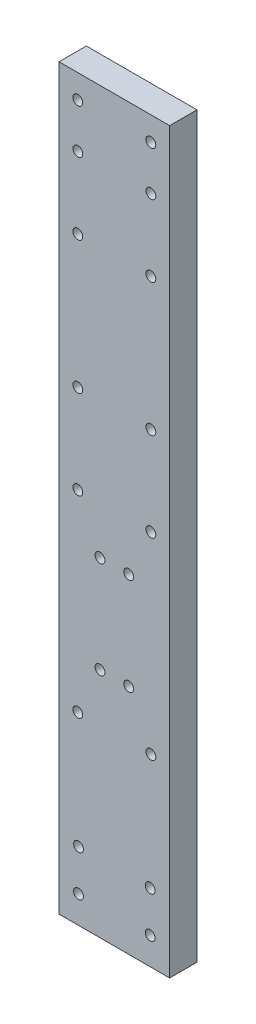
SolidWorks part; units mm, degrees
ref_plane "Front Plane" through (0, 0, 0) normal (0, 0, 1) x (1, 0, 0)
ref_plane "Top Plane" through (0, 0, 0) normal (0, 1, 0) x (1, 0, 0)
ref_plane "Right Plane" through (0, 0, 0) normal (1, 0, 0) x (0, 0, -1)
sketch "Sketch1" plane through (0, 0, 0) normal (0, 0, 1) x (1, 0, 0)
  line L0 (16.2, 0) -> (16.2, 108.14)
  line L1 (16.2, 108.14) -> (0, 108.14)
  line L2 (0, 108.14) -> (0, 0)
  line L3 (0, 0) -> (16.2, 0)
  line L4 (16.2, 57.71) -> (0, 57.71) construction
  line L5 (0, 12.5) -> (16.2, 12.5) construction
  line L6 (0, 24.5) -> (16.2, 24.5) construction
  line L7 (0, 90.16) -> (16.2, 90.16) construction
  line L8 (0, 65.71) -> (16.2, 65.71) construction
  line L9 (8.1, 108.14) -> (8.1, 96.16) construction
  line L11 (0, 96.16) -> (16.2, 96.16) construction
  circle A0 centre (13.45, 55.21) radius 0.72
  circle A1 centre (10.2, 48.21) radius 0.72
  circle A2 centre (13.45, 104.66) radius 0.72
  circle A3 centre (2.75, 98.16) radius 0.72
  circle A4 centre (6, 48.21) radius 0.72
  circle A5 centre (2.75, 27) radius 0.72
  circle A6 centre (2.75, 87.66) radius 0.72
  circle A7 centre (2.75, 55.21) radius 0.72
  circle A8 centre (13.45, 87.66) radius 0.72
  circle A9 centre (13.45, 98.16) radius 0.72
  circle A28 centre (13.45, 68.21) radius 0.72
  circle A29 centre (6, 34) radius 0.72
  circle A32 centre (2.75, 104.66) radius 0.72
  circle A33 centre (10.2, 34) radius 0.72
  circle A34 centre (2.75, 68.21) radius 0.72
  circle A35 centre (13.45, 27) radius 0.72
  circle A36 centre (2.85, 10) radius 0.72
  circle A37 centre (13.35, 10) radius 0.72
  circle A38 centre (13.35, 4) radius 0.72
  circle A39 centre (2.85, 4) radius 0.72
  dimension "D45" = 1.44
  dimension "D1" = 4
  dimension "D2" = 4
  dimension "D3" = 2.85
  dimension "D4" = 2.85
  dimension "D5" = 16.2
  dimension "D6" = 6
  dimension "D7" = 6
  dimension "D8" = 2.85
  dimension "D9" = 2.85
  dimension "D10" = 2.5
  dimension "D11" = 12
  dimension "D12" = 33.21
  dimension "D13" = 2.5
  dimension "D14" = 2.5
  dimension "D15" = 2.75
  dimension "D16" = 2.75
  dimension "D17" = 2.5
  dimension "D18" = 2.5
  dimension "D19" = 2.75
  dimension "D20" = 2.75
  dimension "D21" = 9.5
  dimension "D22" = 6
  dimension "D23" = 9.5
  dimension "D24" = 6
  dimension "D25" = 9.5
  dimension "D26" = 9.5
  dimension "D27" = 6
  dimension "D28" = 6
  dimension "D29" = 8
  dimension "D30" = 24.45
  dimension "D31" = 2.5
  dimension "D32" = 2.5
  dimension "D33" = 2.75
  dimension "D34" = 2.75
  dimension "D35" = 6
  dimension "D36" = 2.75
  dimension "D37" = 2
  dimension "D38" = 2.75
  dimension "D39" = 8.5
  dimension "D40" = 11.98
  dimension "D41" = 2.5
  dimension "D42" = 2.5
  dimension "D43" = 2.75
  dimension "D44" = 2.75
extrude "Boss-Extrude1" add sketch "Sketch1" along normal blind 4
equation "\"D12@Sketch1\"= \"HL@parametersSketch@prostheticParameters.SLDPRT\" * 0.266 - 12 - 4 'Middle PIP Length"
equation "\"D30@Sketch1\"= \"HL@parametersSketch@prostheticParameters.SLDPRT\" * 0.17 - 4 - 3'Middle MIP Length"
equation "\"D5@Sketch1\"= \"fingerWidth@parametersSketch@prostheticParameters.SLDPRT\" 'Middle Width"
equation "\"D40@Sketch1\"= \"HL@parametersSketch@prostheticParameters.SLDPRT\" * 0.108 - 3 - 5'Middle DIP Length"
equation "\"D45@Sketch1\"= 1.04 + \"tol1@parametersSketch@prostheticParameters.SLDPRT\""
